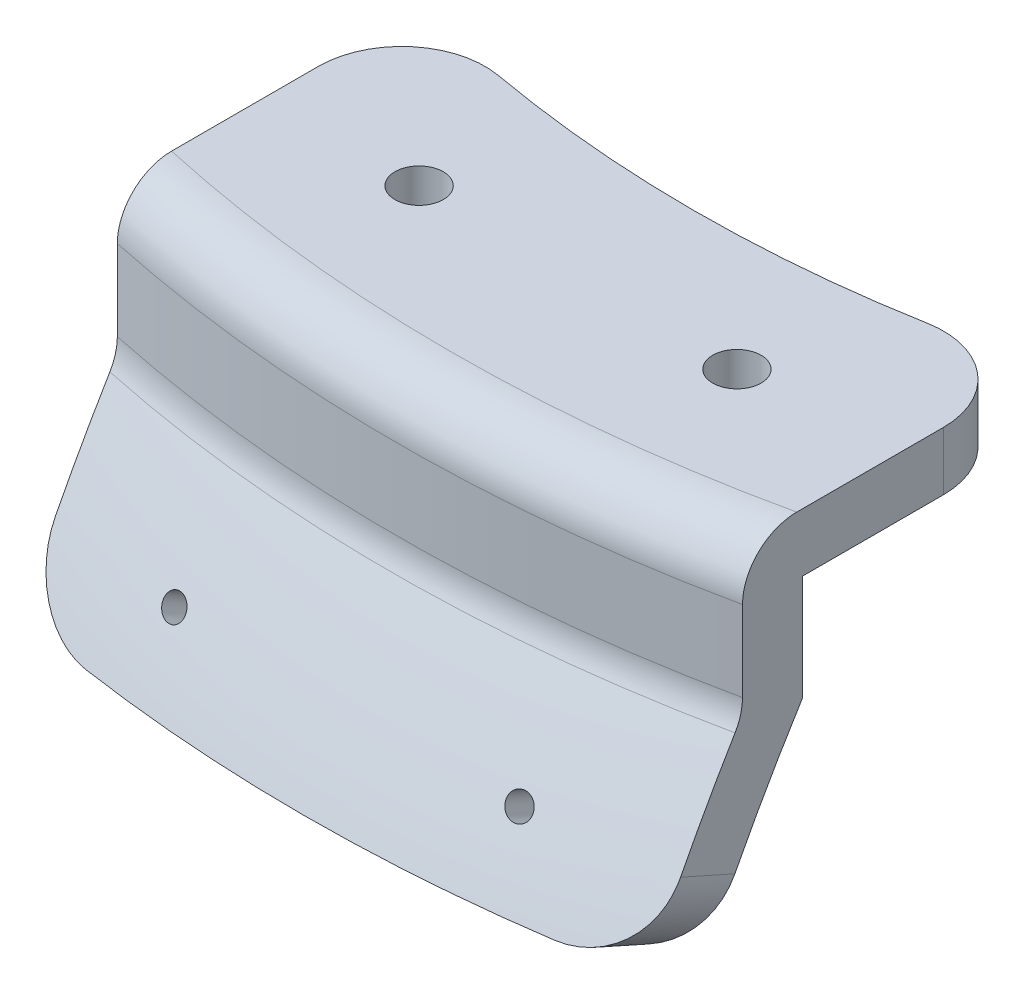
SolidWorks part; units mm, degrees
material "Polyether Polyol"
ref_plane "Front Plane" through (0, 0, 0) normal (0, 0, 1) x (1, 0, 0)
ref_plane "Top Plane" through (0, 0, 0) normal (0, 1, 0) x (1, 0, 0)
ref_plane "Right Plane" through (0, 0, 0) normal (1, 0, 0) x (0, 0, -1)
sketch "Sketch2" plane through (0, 0, 0) normal (1, 0, 0) x (0, 0, -1)
  line L0 (-173.3622, 178.8688) -> (-173.3622, 166.1688) construction
  line L1 (-191.634, 146.5436) -> (-185.2523, 143.6672) construction
  line L2 (-180.3622, 185.8688) -> (-180.3622, 168.1213) construction
  line L3 (-180.3622, 185.8688) -> (-144.7872, 185.8688) construction
  line L4 (-144.7872, 185.8688) -> (-144.7872, 178.8688) construction
  line L5 (-144.7872, 178.8688) -> (-173.3622, 178.8688) construction
  line L12 (0, 60.1698) -> (0, 178.8688) construction
  line L13 (-173.3622, 178.8688) -> (-173.3622, 166.1688)
  line L14 (-191.634, 146.5436) -> (-185.2523, 143.6672)
  line L15 (-180.3622, 185.8688) -> (-180.3622, 168.1213)
  line L16 (-180.3622, 185.8688) -> (-144.7872, 185.8688)
  line L17 (-144.7872, 185.8688) -> (-144.7872, 178.8688)
  line L18 (-144.7872, 178.8688) -> (-173.3622, 178.8688)
  arc A0 (-173.3622, 166.1688) -> (-185.2523, 143.6672) centre (0, 60.1698) ccw construction
  arc A1 (-180.3622, 168.1213) -> (-191.634, 146.5436) centre (0, 60.1698) ccw construction
  arc A4 (-173.3622, 166.1688) -> (-185.2523, 143.6672) centre (0, 60.1698) ccw
  arc A5 (-180.3622, 168.1213) -> (-191.634, 146.5436) centre (0, 60.1698) ccw
revolve "Revolve1" add sketch "Sketch2" angle 30 mid plane about L12
fillet "Fillet1" radius 6.35 2 edges at (0, 168.1213, 180.3622) (0, 185.8688, 180.3622)
sketch "Sketch3" plane through (0, 185.8688, 0) normal (0, -1, 0) x (1, 0, 0)
  circle A2 centre (-19.05, 158.6742) radius 3.5719 construction
  circle A3 centre (19.05, 158.6742) radius 3.5719 construction
  circle A4 centre (19.05, 158.6742) radius 2.9
  circle A5 centre (-19.05, 158.6742) radius 2.9
  point P1 (-19.05, 158.6742)
  point P3 (19.05, 158.6742)
  dimension "D1" = 5.8
extrude "Cut-Extrude1" cut sketch "Sketch3" along normal through all contours A4 | A5 region at (19.05, 185.8688, 158.6742) region at (-19.05, 185.8688, 158.6742)
sketch "Sketch4" plane through (0, 185.8688, 0) normal (0, 1, 0) x (1, 0, 0)
  line L0 (37.4737, -139.8537) -> (45.0377, -168.0828) construction
  line L1 (37.4737, -139.8537) -> (-37.4737, -139.8537)
  line L2 (37.4737, -139.8537) -> (37.4737, -191.634)
  line L3 (37.4737, -191.634) -> (-37.4737, -191.634)
  line L4 (-37.4737, -139.8537) -> (-37.4737, -191.634)
  line L5 (-37.4737, -139.8537) -> (-45.0377, -168.0828) construction
  arc A0 (-37.4737, -139.8537) -> (37.4737, -139.8537) centre (0, 0) ccw construction
  arc A1 (-49.5985, -185.1043) -> (49.5985, -185.1043) centre (0, 0) ccw construction
extrude "Cut-Extrude2" cut sketch "Sketch4" against normal through all flip side to cut
fillet "Fillet2" radius 10 4 edges at (-37.4737, 182.3688, 139.8537) (37.4737, 182.3688, 139.8537)
sketch "Sketch5" plane through (0, 0, 0) normal (-1, 0, 0) x (0, 0, 1)
  line L0 (0, 60.1698) -> (181.0525, 152.4206) construction
  line L2 (0, -200000) -> (0, 218797.9879) construction
  arc A0 (185.2523, 143.6672) -> (173.3622, 166.1688) centre (0, 60.1698) ccw construction
  dimension "D1" = 63
ref_plane "Plane1" through (0, 47.7683, -24.3392) normal (0, 0.891, -0.454) x (0, 0.454, 0.891)
sketch "Sketch6" plane through (0, 47.7683, -24.3392) normal (0, 0.891, -0.454) x (0, 0.454, 0.891)
  line L0 (203.4667, 17.801) -> (275.7942, 24.1289) construction
  line L2 (203.4667, 17.801) -> (275.7942, 24.1289)
  line L3 (203.4667, 17.801) -> (203.3359, 19.2953)
  line L4 (275.7942, 24.1289) -> (275.6635, 25.6232)
  line L5 (203.3359, 19.2953) -> (275.6635, 25.6232)
  line L6 (27.3165, 0) -> (230.5165, 0) construction
  ellipse E0 centre (75.4391, 0) end of major axis (75.4391, 144.7872) minor radius 129.0063 construction
  dimension "D1" = 5
  dimension "D2" = 1.5
revolve "Cut-Revolve1" cut sketch "Sketch6" angle 360 about L0
mirror "Mirror1" about plane through (0, 0, 0) normal (1, 0, 0) of "Cut-Revolve1"
